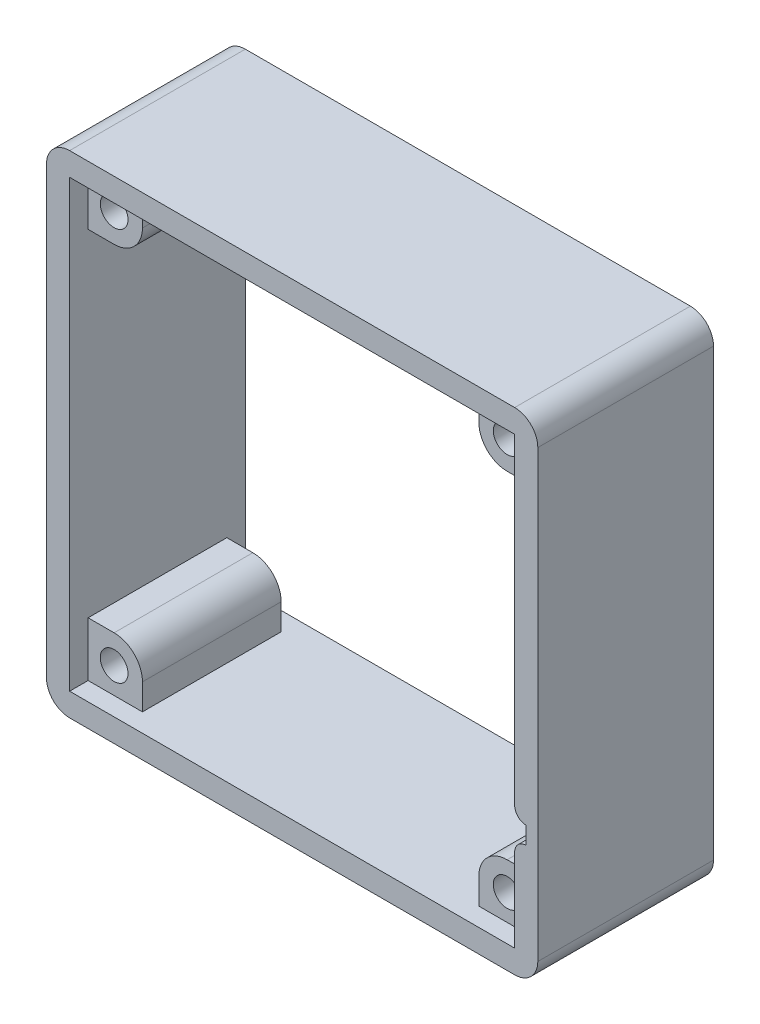
SolidWorks part; units mm, degrees
ref_plane "Front Plane" through (0, 0, 0) normal (0, 0, 1) x (1, 0, 0)
ref_plane "Top Plane" through (0, 0, 0) normal (0, 1, 0) x (1, 0, 0)
ref_plane "Right Plane" through (0, 0, 0) normal (1, 0, 0) x (0, 0, -1)
sketch "Sketch1" plane through (0, 0, 0) normal (0, 0, 1) x (1, 0, 0)
  line L0 (19.05, -19.05) -> (19.05, 19.05) construction
  line L5 (21.25, 21.25) -> (-21.25, 21.25)
  line L6 (-21.25, 21.25) -> (-21.25, -21.25)
  line L7 (-19.05, -19.05) -> (19.05, -19.05) construction
  line L8 (-19.05, 19.05) -> (-19.05, -19.05) construction
  line L9 (19.05, 19.05) -> (-19.05, 19.05) construction
  line L10 (19.05, -19.05) -> (19.05, 19.05) construction
  line L11 (-19.05, -19.05) -> (19.05, -19.05) construction
  line L12 (-19.05, 19.05) -> (-19.05, -19.05) construction
  line L13 (19.05, 19.05) -> (-19.05, 19.05) construction
  line L14 (19.25, -19.25) -> (19.25, 19.25)
  line L15 (19.25, 19.25) -> (-19.25, 19.25)
  line L16 (-19.25, 19.25) -> (-19.25, -19.25)
  line L17 (-19.25, -19.25) -> (19.25, -19.25)
  line L18 (-21.25, -21.25) -> (21.25, -21.25)
  line L19 (21.25, -21.25) -> (21.25, 21.25)
  point P336 (-1.13, 0.5101)
  dimension "D2" = 2
  dimension "D1" = 0.2
extrude "Boss-Extrude2" add sketch "Sketch1" against normal up to surface (15.2 mm away)
sketch "Sketch2" plane through (0, 0, -1.6) normal (0, 0, -1) x (-1, 0, 0)
  line L0 (17, -14.55) -> (19.25, -14.55)
  line L1 (19.25, 19.25) -> (19.25, -19.25) construction
  line L2 (14.55, -17) -> (14.55, -19.25)
  line L3 (19.25, -19.25) -> (-19.25, -19.25) construction
  line L4 (19.25, -19.25) -> (14.55, -19.25)
  line L5 (19.25, -14.55) -> (19.25, -19.25)
  line L6 (19.05, -19.05) -> (-19.05, -19.05) construction
  line L7 (0, 0) -> (-50000, 0) construction
  line L8 (0, 0) -> (0, 50000) construction
  line L9 (19.25, 14.55) -> (19.25, 19.25)
  line L10 (19.25, 19.25) -> (14.55, 19.25)
  line L11 (14.55, 17) -> (14.55, 19.25)
  line L12 (17, 14.55) -> (19.25, 14.55)
  line L13 (-19.25, -14.55) -> (-19.25, -19.25)
  line L14 (-19.25, -19.25) -> (-14.55, -19.25)
  line L15 (-14.55, -17) -> (-14.55, -19.25)
  line L16 (-17, -14.55) -> (-19.25, -14.55)
  line L17 (-17, 14.55) -> (-19.25, 14.55)
  line L18 (-14.55, 17) -> (-14.55, 19.25)
  line L19 (-19.25, 19.25) -> (-14.55, 19.25)
  line L20 (-19.25, 14.55) -> (-19.25, 19.25)
  circle A2 centre (17, -17) radius 1.2 construction
  circle A3 centre (17, -17) radius 1.2
  arc A4 (17, -14.55) -> (14.55, -17) centre (17, -17) ccw
  arc A5 (17, 14.55) -> (14.55, 17) centre (17, 17) cw
  circle A6 centre (17, 17) radius 1.2
  arc A7 (-17, -14.55) -> (-14.55, -17) centre (-17, -17) cw
  circle A8 centre (-17, -17) radius 1.2
  circle A9 centre (-17, 17) radius 1.2
  arc A10 (-17, 14.55) -> (-14.55, 17) centre (-17, 17) ccw
  dimension "D1" = 4.5
extrude "Boss-Extrude4" add sketch "Sketch2" along normal up to surface (12 mm away) up to face at (0, 0, 0)
fillet "Fillet1" radius 2 4 edges at (-21.25, 21.25, -7.6) (21.25, 21.25, -7.6) (21.25, -21.25, -7.6) (-21.25, -21.25, -7.6)
sketch "Sketch3" plane through (0, 0, 0) normal (0, 0, 1) x (1, 0, 0)
  line L0 (20.25, -11.05) -> (20.25, -9.55) construction
  line L1 (20.25, -11.05) -> (20.25, -9.55)
  line L2 (19.25, -8.55) -> (19.25, -12.05)
  arc A0 (19.25, -8.55) -> (20.25, -9.55) centre (20.25, -8.55) ccw construction
  arc A1 (20.25, -11.05) -> (19.25, -12.05) centre (20.25, -12.05) ccw construction
  arc A2 (19.25, -8.55) -> (20.25, -9.55) centre (20.25, -8.55) ccw
  arc A3 (20.25, -11.05) -> (19.25, -12.05) centre (20.25, -12.05) ccw
extrude "Cut-Extrude2" cut sketch "Sketch3" against normal blind 4
